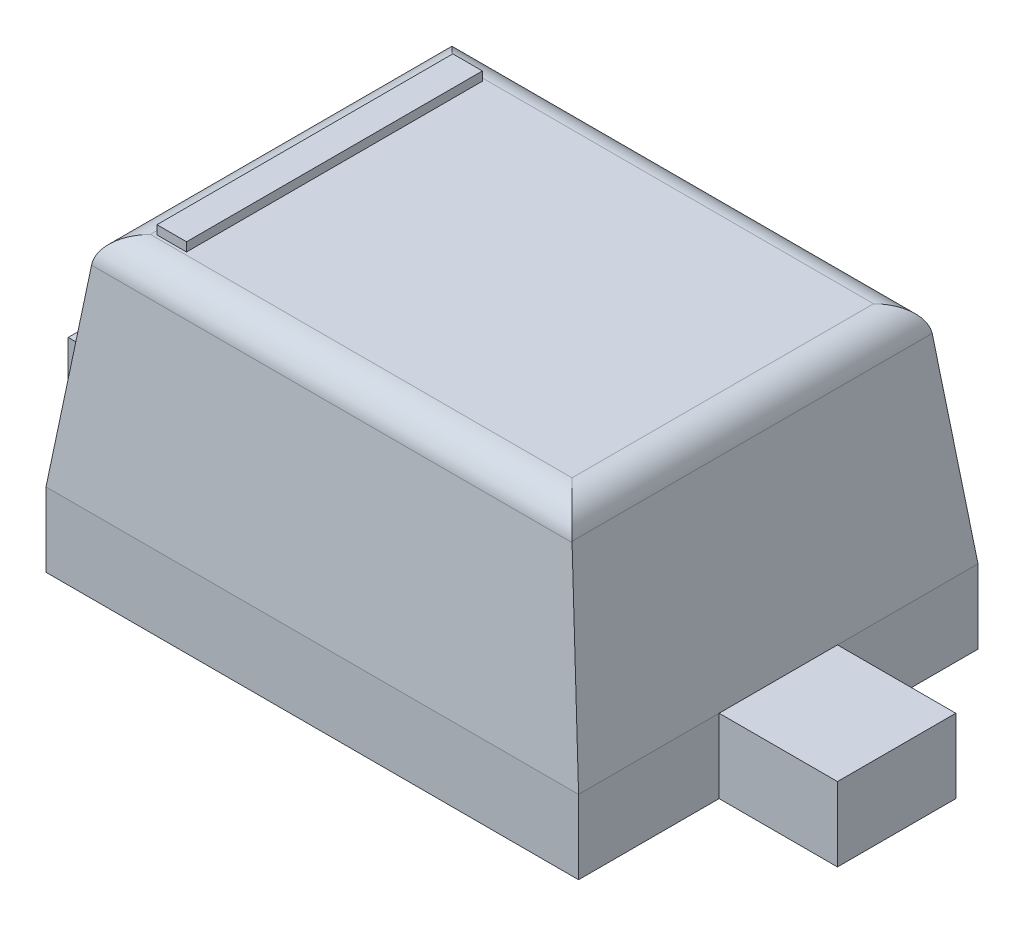
SolidWorks part; units mm, degrees
ref_plane "Спереди" through (0, 0, 0) normal (0, 0, 1) x (1, 0, 0)
ref_plane "Сверху" through (0, 0, 0) normal (0, 1, 0) x (1, 0, 0)
ref_plane "Справа" through (0, 0, 0) normal (1, 0, 0) x (0, 0, -1)
sketch "Эскиз1" plane through (0, 0, 0) normal (0, 1, 0) x (1, 0, 0)
  line L1 (-0.9, 0.675) -> (0.9, 0.675)
  line L2 (-0.9, 0.675) -> (-0.9, -0.675)
  line L3 (-0.9, -0.675) -> (0.9, -0.675)
  line L4 (0.9, 0.675) -> (0.9, -0.675)
  line L5 (-0.9, 0.675) -> (0.9, -0.675) construction
  line L6 (-0.9, -0.675) -> (0.9, 0.675) construction
  point P0 (0, 0)
extrude "Бобышка-Вытянуть1" add sketch "Эскиз1" along normal blind 0.25
sketch "Эскиз2" plane through (0, 0, 0) normal (0, 1, 0) x (1, 0, 0)
  line L0 (0.9, -0.675) -> (0.9, 0.675) construction
  line L1 (0.5, 0.2) -> (1.3, 0.2)
  line L2 (0.5, 0.2) -> (0.5, -0.2)
  line L3 (0.5, -0.2) -> (1.3, -0.2)
  line L4 (1.3, 0.2) -> (1.3, -0.2)
  line L5 (0.5, 0.2) -> (1.3, -0.2) construction
  line L6 (0.5, -0.2) -> (1.3, 0.2) construction
  line L7 (-0.9, 0.675) -> (-0.9, -0.675) construction
  line L8 (-0.5, 0.2) -> (-1.3, 0.2)
  line L9 (-0.5, 0.2) -> (-0.5, -0.2)
  line L10 (-0.5, -0.2) -> (-1.3, -0.2)
  line L11 (-1.3, 0.2) -> (-1.3, -0.2)
  line L12 (-0.5, 0.2) -> (-1.3, -0.2) construction
  line L13 (-0.5, -0.2) -> (-1.3, 0.2) construction
  point P0 (0.9, 0)
  point P7 (-0.9, 0)
extrude "Бобышка-Вытянуть2" add sketch "Эскиз2" along normal blind 0.25 separate body
combine bodies "Соединить1" operation type subtract main body 103 bodies to subtract 105 104
extrude "Бобышка-Вытянуть3" add sketch "Эскиз2<2>" along normal blind 0.25 separate body
sketch "Эскиз2<2>" plane through (0, 0, 0) normal (0, 1, 0) x (1, 0, 0) same geometry as "Эскиз2"
sketch "Эскиз3" plane through (0, 0.25, 0) normal (0, 1, 0) x (1, 0, 0)
  line L1 (0.9, -0.675) -> (-0.9, -0.675)
  line L2 (0.9, -0.675) -> (0.9, 0.675)
  line L3 (0.9, 0.675) -> (-0.9, 0.675)
  line L4 (-0.9, -0.675) -> (-0.9, 0.675)
  line L5 (0.9, -0.675) -> (-0.9, 0.675) construction
  line L6 (0.9, 0.675) -> (-0.9, -0.675) construction
  point P0 (0, 0)
ref_plane "Плоскость1" through (0, 1, 0) normal (0, 1, 0) x (1, 0, 0)
sketch "Эскиз4" plane through (0, 1, 0) normal (0, 1, 0) x (1, 0, 0)
  line L1 (0.8, -0.6) -> (-0.8, -0.6)
  line L2 (0.8, -0.6) -> (0.8, 0.6)
  line L3 (0.8, 0.6) -> (-0.8, 0.6)
  line L4 (-0.8, -0.6) -> (-0.8, 0.6)
  line L5 (0.8, -0.6) -> (-0.8, 0.6) construction
  line L6 (0.8, 0.6) -> (-0.8, -0.6) construction
  point P0 (0, 0)
loft "По сечениям1" add profiles "Эскиз3", "Эскиз4" connector at (-0.9, 0.25, 0.675) connector at (-0.8, 1, 0.6)
sketch "Эскиз5" plane through (0, 1, 0) normal (0, 1, 0) x (1, 0, 0)
  line L1 (-0.7, 0.5) -> (-0.6, 0.5)
  line L2 (-0.7, 0.5) -> (-0.7, -0.5)
  line L3 (-0.7, -0.5) -> (-0.6, -0.5)
  line L4 (-0.6, 0.5) -> (-0.6, -0.5)
  point P4 (0, 0)
  point P5 (0, 0)
extrude "Бобышка-Вытянуть4" add sketch "Эскиз5" along normal blind 0.03 separate body
fillet "Скругление1" radius 0.1 4 edges
